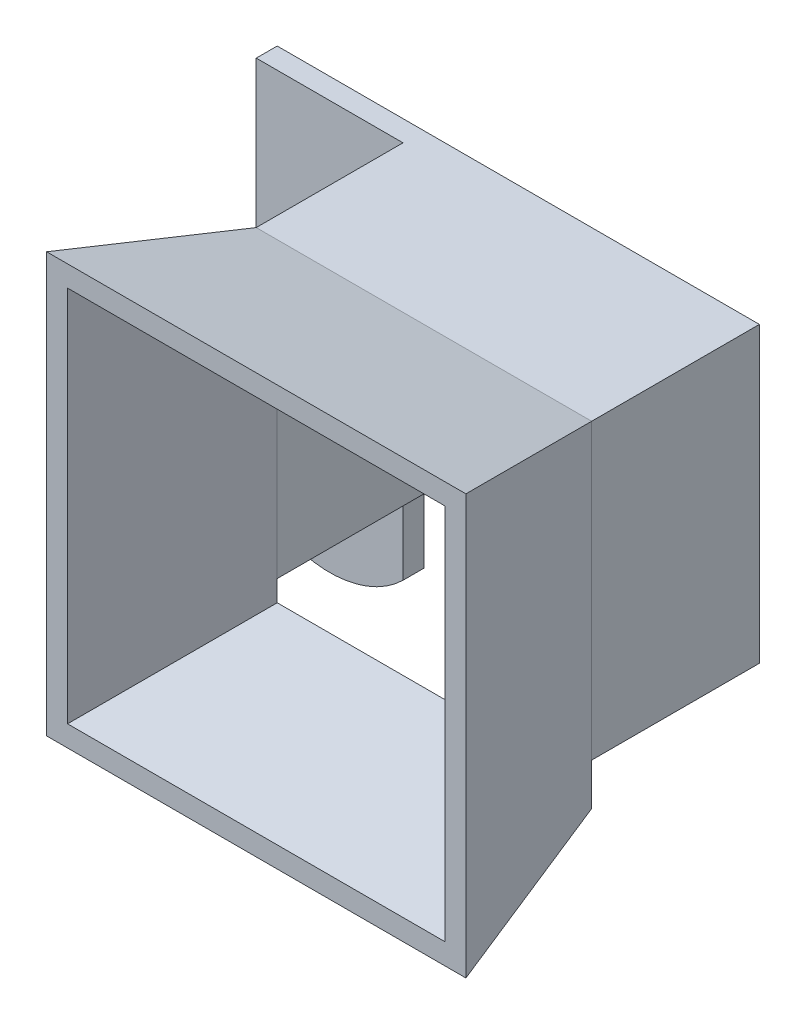
SolidWorks part; units mm, degrees
material "ABS"
ref_plane "Front Plane" through (0, 0, 0) normal (0, 0, 1) x (1, 0, 0)
ref_plane "Top Plane" through (0, 0, 0) normal (0, 1, 0) x (1, 0, 0)
ref_plane "Right Plane" through (0, 0, 0) normal (1, 0, 0) x (0, 0, -1)
sketch "Sketch2" plane through (0, 0, 0) normal (0, 0, 1) x (1, 0, 0)
  line L0 (0, 0) -> (69.8407, 0) construction
  line L1 (-50.8, 50.8) -> (50.8, 50.8)
  line L2 (-50.8, 50.8) -> (-50.8, -50.8)
  line L3 (-50.8, -50.8) -> (50.8, -50.8)
  line L4 (50.8, 50.8) -> (50.8, -50.8)
  line L5 (0, 0) -> (0, -80.5593) construction
  dimension "D1" = 101.6
ref_plane "Plane1" through (0, 0, 50.8) normal (0, 0, 1) x (1, 0, 0)
sketch "Sketch3" plane through (0, 0, 50.8) normal (0, 0, 1) x (1, 0, 0)
  line L0 (0, 0) -> (0, 42.9934) construction
  line L1 (-63.5, 63.5) -> (63.5, 63.5)
  line L2 (-63.5, 63.5) -> (-63.5, -63.5)
  line L3 (-63.5, -63.5) -> (63.5, -63.5)
  line L4 (63.5, 63.5) -> (63.5, -63.5)
  line L7 (0, 0) -> (38.1349, 0) construction
  dimension "D1" = 127
loft "Loft1" add profiles "Sketch2", "Sketch3" connector at (50.8, 50.8, 0) connector at (63.5, 63.5, 50.8)
sketch "Sketch4" plane through (0, 0, 50.8) normal (0, 0, 1) x (1, 0, 0)
  line L14 (-57.15, -57.15) -> (57.15, -57.15)
  line L15 (57.15, -57.15) -> (57.15, 57.15)
  line L16 (57.15, 57.15) -> (-57.15, 57.15)
  line L17 (-57.15, 57.15) -> (-57.15, -57.15)
  line L18 (-57.15, -57.15) -> (57.15, -57.15)
  line L19 (57.15, -57.15) -> (57.15, 57.15)
  line L20 (57.15, 57.15) -> (-57.15, 57.15)
  line L21 (-57.15, 57.15) -> (-57.15, -57.15)
  dimension "D1" = 6.35
sketch "Sketch5" plane through (0, 0, 0) normal (0, 0, -1) x (-1, 0, 0)
  line L14 (-44.45, -44.45) -> (44.45, -44.45)
  line L15 (44.45, -44.45) -> (44.45, 44.45)
  line L16 (44.45, 44.45) -> (-44.45, 44.45)
  line L17 (-44.45, 44.45) -> (-44.45, -44.45)
  line L18 (-44.45, -44.45) -> (44.45, -44.45)
  line L19 (44.45, -44.45) -> (44.45, 44.45)
  line L20 (44.45, 44.45) -> (-44.45, 44.45)
  line L21 (-44.45, 44.45) -> (-44.45, -44.45)
  dimension "D1" = 6.35
loft "Cut-Loft1" cut profiles "Sketch5", "Sketch4" connector at (-44.45, 44.45, 0) connector at (-57.15, 57.15, 50.8)
sketch "Sketch6" plane through (0, 0, 0) normal (0, 0, -1) x (-1, 0, 0)
  line L0 (44.45, -38.1) -> (50.8, -38.1)
  line L1 (44.45, -44.45) -> (44.45, 44.45) construction
  line L2 (50.8, 50.8) -> (50.8, -50.8) construction
  line L3 (50.8, -38.1) -> (50.8, 50.8)
  line L4 (50.8, 50.8) -> (-50.8, 50.8)
  line L5 (-50.8, 50.8) -> (-50.8, -38.1)
  line L6 (-50.8, -50.8) -> (-50.8, 50.8) construction
  line L7 (-50.8, -38.1) -> (-44.45, -38.1)
  line L8 (-44.45, 44.45) -> (-44.45, -44.45) construction
  line L9 (-44.45, -38.1) -> (-44.45, 44.45)
  line L10 (-44.45, 44.45) -> (44.45, 44.45)
  line L11 (44.45, 44.45) -> (44.45, -38.1)
  line L12 (44.45, -38.1) -> (38.1, -38.1) construction
  line L13 (-44.45, -38.1) -> (-38.1, -38.1) construction
extrude "Boss-Extrude1" add sketch "Sketch6" along normal blind 50.8
sketch "Sketch7" plane through (0, 0, -50.8) normal (0, 0, -1) x (-1, 0, 0)
  line L0 (50.8, 50.8) -> (-50.8, 50.8) construction
  line L1 (44.45, -38.1) -> (95.25, -38.1)
  line L2 (44.45, -38.1) -> (44.45, 50.8)
  line L3 (44.45, 50.8) -> (95.25, 50.8)
  line L4 (95.25, -38.1) -> (95.25, 50.8)
  dimension "D1" = 50.8
extrude "Boss-Extrude2" add sketch "Sketch7" against normal blind 6.35
sketch "Sketch8" plane through (0, 0, -44.45) normal (0, 0, 1) x (1, 0, 0)
  line L0 (-50.8, 50.8) -> (-50.8, -38.1) construction
  line L1 (-95.25, -38.1) -> (-50.8, -38.1)
  line L2 (-95.25, -38.1) -> (-95.25, -76.2)
  line L3 (-95.25, -76.2) -> (-50.8, -76.2)
  line L4 (-50.8, -38.1) -> (-50.8, -76.2)
  dimension "D1" = 38.1
extrude "Boss-Extrude3" add sketch "Sketch8" against normal up to surface (6.35 mm away) up to face at (-11.1125, 4.7625, -50.8)
fillet "Fillet1" [suppressed] radius 35.56
sketch "Sketch9" plane through (0, 0, -44.45) normal (0, 0, 1) x (1, 0, 0)
  line L0 (-73.025, 27.6092) -> (-73.025, -57.5144) construction
  line L3 (-62.992, -50.3) -> (-62.992, -11.041) construction
  line L4 (-83.185, -10.3505) -> (-62.865, -10.3505)
  line L5 (-83.185, -10.3505) -> (-83.185, -50.9905)
  line L6 (-83.185, -50.9905) -> (-62.865, -50.9905)
  line L7 (-62.865, -10.3505) -> (-62.865, -50.9905)
  line L8 (-83.058, -11.041) -> (-83.058, -50.3) construction
  line L9 (-89.9768, -30.6705) -> (-55.7405, -30.6705) construction
  line L10 (-82.558, -50.8) -> (-63.492, -50.8) construction
  line L11 (-63.492, -10.541) -> (-82.558, -10.541) construction
  dimension "D1" = 20.32
  dimension "D2" = 40.64
fillet "Fillet2" [suppressed] radius 2.54
extrude "Cut-Extrude1" cut sketch "Sketch9" against normal through all
sketch "Sketch10" plane through (0, 0, -44.45) normal (0, 0, 1) x (1, 0, 0)
  circle A0 centre (-68.025, -6.1705) radius 1.778
  circle A1 centre (-78.025, -6.1705) radius 1.778
  circle A2 centre (-78.025, -55.1705) radius 1.778
  circle A3 centre (-68.025, -55.1705) radius 1.778
  arc A4 (-76.755, -56.4148) -> (-79.295, -56.4148) centre (-78.025, -55.1705) ccw construction
  arc A5 (-66.755, -56.4148) -> (-69.295, -56.4148) centre (-68.025, -55.1705) ccw construction
  arc A6 (-79.295, -4.9262) -> (-76.755, -4.9262) centre (-78.025, -6.1705) ccw construction
  arc A7 (-69.295, -4.9262) -> (-66.755, -4.9262) centre (-68.025, -6.1705) ccw construction
extrude "Cut-Extrude2" cut sketch "Sketch10" against normal through all
sketch "Sketch11" plane through (0, 0, -44.45) normal (0, 0, 1) x (1, 0, 0)
  line L0 (-50.8, -76.2) -> (-95.25, -76.2)
  line L1 (-95.25, -76.2) -> (-50.8, -76.2) construction
  line L2 (-95.25, -76.2) -> (-95.25, -63.949)
  line L3 (-95.25, -76.2) -> (-95.25, 50.8) construction
  line L4 (-50.8, -76.2) -> (-50.8, -63.949)
  line L5 (-50.8, -76.2) -> (-50.8, -38.1) construction
  circle A0 centre (-73.025, -41.275) radius 31.75
  circle A1 centre (-73.025, -41.275) radius 6.25 construction
  line M11 (-95.25, 50.8) -> (-95.25, -76.2)
  line M12 (-95.25, -76.2) -> (-50.8, -76.2)
  line M13 (-50.8, -76.2) -> (-50.8, -38.1)
  dimension "D1" = 63.5
extrude "Cut-Extrude3" cut sketch "Sketch11" against normal blind 6.35 contours A0 M11 M12 M13 region at (-73.025, -75.7389, -44.45)
